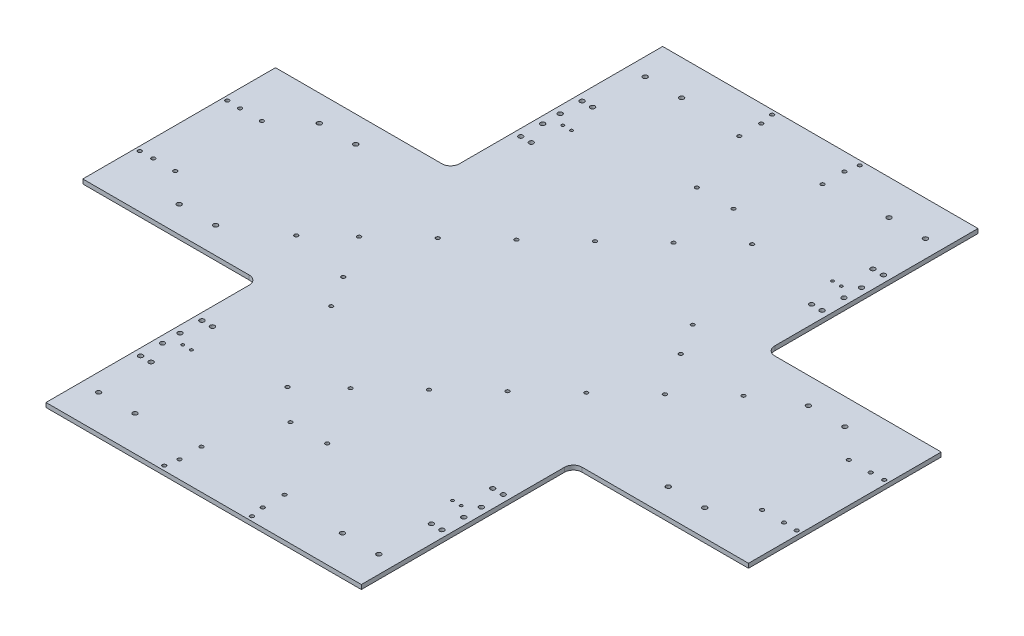
SolidWorks part; units mm, degrees
other "Markup1"
sketch "Sketch8"
material "3.0205 (EN-AW 1200)"
ref_plane "前视基准面" through (0, 0, 0) normal (0, 0, 1) x (1, 0, 0)
ref_plane "上视基准面" through (0, 0, 0) normal (0, 1, 0) x (1, 0, 0)
ref_plane "右视基准面" through (0, 0, 0) normal (1, 0, 0) x (0, 0, -1)
other "Configuration Table"
sketch "Sketch1" plane through (0, 0, 0) normal (0, 1, 0) x (1, 0, 0)
  line L0 (180, 352) -> (-180, 352)
  line L1 (-180, 352) -> (-180, 110)
  line L2 (-180, 110) -> (-380, 110)
  line L5 (-380, 110) -> (-380, -110)
  line L6 (0, 352) -> (0, -66.8675) construction
  line L7 (-380, 0) -> (131.0517, 0) construction
  line L8 (380, 110) -> (380, -110)
  line L11 (180, 110) -> (380, 110)
  line L12 (180, 352) -> (180, 110)
  line L13 (180, -352) -> (180, -110)
  line L14 (180, -110) -> (380, -110)
  line L19 (-180, -110) -> (-380, -110)
  line L20 (-180, -352) -> (-180, -110)
  line L21 (180, -352) -> (-180, -352)
  point P21 (380, 0)
  dimension "D1" = 180
  dimension "D2" = 200
  dimension "D3" = 110
  dimension "D4" = 242
extrude "Boss-Extrude1" add sketch "Sketch1" along normal blind 5
sketch "Sketch2" plane through (0, 5, 0) normal (0, 1, 0) x (1, 0, 0)
  line L3 (380, -110) -> (380, 110) construction
  line L4 (-56.7455, 0) -> (47.5165, 0) construction
  line L5 (0, 54.7142) -> (0, -64.2255) construction
  line L7 (180, 352) -> (-180, 352) construction
  circle A0 centre (360, 49.5) radius 2.125
  circle A1 centre (335, 49.5) radius 2.125
  circle A7 centre (335, -49.5) radius 2.125
  circle A8 centre (360, -49.5) radius 2.125
  circle A9 centre (-360, -49.5) radius 2.125
  circle A10 centre (-335, -49.5) radius 2.125
  circle A13 centre (-335, 49.5) radius 2.125
  circle A14 centre (-360, 49.5) radius 2.125
  circle A15 centre (47.5, 332) radius 2.125
  circle A16 centre (47.5, 307) radius 2.125
  circle A17 centre (-47.5, 307) radius 2.125
  circle A18 centre (-47.5, 332) radius 2.125
  circle A19 centre (-47.5, -332) radius 2.125
  circle A20 centre (-47.5, -307) radius 2.125
  circle A21 centre (47.5, -307) radius 2.125
  circle A22 centre (47.5, -332) radius 2.125
  dimension "D3" = 49.5
  dimension "D5" = 4.25
  dimension "D7" = 4.25
  dimension "D9" = 4.25
  dimension "D10" = 4.25
  dimension "D2" = 47.5
  dimension "D4" = 25
  dimension "D6" = 20
  dimension "20" = 20
  dimension "D13" = 25
extrude "Cut-Extrude1" cut sketch "Sketch2" against normal blind 3
sketch "Sketch4" plane through (0, 5, 0) normal (0, 1, 0) x (1, 0, 0)
  line L0 (-180, 352) -> (-180, 110) construction
  line L1 (180, 352) -> (-180, 352) construction
  line L2 (0, 46.9886) -> (0, -40.2904) construction
  line L3 (-35.103, 0) -> (92.4951, 0) construction
  line L5 (180, -352) -> (180, -110) construction
  circle A0 centre (-172, 182) radius 2.6
  circle A1 centre (-160, 182) radius 2.6
  circle A2 centre (-172, 207) radius 2.6
  circle A3 centre (-172, 227) radius 2.6
  circle A4 centre (-172, 252) radius 2.6
  circle A5 centre (-160, 252) radius 2.6
  circle A6 centre (160, 252) radius 2.6
  circle A7 centre (172, 252) radius 2.6
  circle A8 centre (172, 227) radius 2.6
  circle A9 centre (172, 207) radius 2.6
  circle A10 centre (160, 182) radius 2.6
  circle A11 centre (172, 182) radius 2.6
  circle A12 centre (172, -182) radius 2.6
  circle A13 centre (160, -182) radius 2.6
  circle A14 centre (172, -207) radius 2.6
  circle A15 centre (172, -227) radius 2.6
  circle A16 centre (172, -252) radius 2.6
  circle A17 centre (160, -252) radius 2.6
  circle A18 centre (-160, -252) radius 2.6
  circle A19 centre (-172, -252) radius 2.6
  circle A20 centre (-172, -227) radius 2.6
  circle A21 centre (-172, -207) radius 2.6
  circle A22 centre (-160, -182) radius 2.6
  circle A23 centre (-172, -182) radius 2.6
  circle A24 centre (159, -217) radius 1.6
  circle A25 centre (-159, -217) radius 1.6
  circle A26 centre (159, 217) radius 1.6
  circle A27 centre (-159, 217) radius 1.6
  circle A28 centre (149, -217) radius 1.6
  circle A29 centre (-149, -217) radius 1.6
  circle A30 centre (149, 217) radius 1.6
  circle A31 centre (-149, 217) radius 1.6
  dimension "D3" = 5.2
  dimension "D4" = 5.2
  dimension "D5" = 8
  dimension "D6" = 8
  dimension "D9" = 5.2
  dimension "D10" = 5.2
  dimension "D11" = 5.2
  dimension "D12" = 5.2
  dimension "D19" = 3.2
  dimension "D20" = 21
  dimension "D21" = 10
  dimension "D22" = 3.2
  dimension "D23" = 10
  dimension "D1" = 8
  dimension "D2" = 20
  dimension "D7" = 8
  dimension "D8" = 20
  dimension "D13" = 25
  dimension "D14" = 20
  dimension "D15" = 25
  dimension "D16" = 25
  dimension "D17" = 100
  dimension "D18" = 0
extrude "Cut-Extrude3" cut sketch "Sketch4" against normal blind 10
sketch "Sketch5" plane through (0, 5, 0) normal (0, 1, 0) x (1, 0, 0)
  line L0 (180, 352) -> (-180, 352) construction
  line L5 (-46.9195, 0) -> (66.6223, 0) construction
  line L6 (0, 59.0569) -> (0, -54.4849) construction
  line L10 (-380, 110) -> (-380, -110) construction
  circle A0 centre (-50, 347) radius 2.125
  circle A1 centre (50, 347) radius 2.125
  circle A2 centre (50, -347) radius 2.125
  circle A3 centre (-50, -347) radius 2.125
  circle A4 centre (-375, 50) radius 2.125
  circle A5 centre (-375, -50) radius 2.125
  circle A6 centre (375, -50) radius 2.125
  circle A7 centre (375, 50) radius 2.125
  dimension "D1" = 4.25
  dimension "D2" = 4.25
  dimension "D3" = 50
  dimension "D6" = 4.25
  dimension "D7" = 4.25
  dimension "5" = 5
  dimension "D4" = 50
  dimension "D5" = 50
  dimension "D8" = 50
  dimension "D9" = 5
  dimension "D10" = 5
extrude "Cut-Extrude4" cut sketch "Sketch5" against normal blind 10
fillet "Fillet1" radius 10 4 edges at (-180, 2.5, -110) (-180, 2.5, 110) (180, 2.5, 110) (180, 2.5, -110)
sketch "Sketch6" plane through (0, 5, 0) normal (0, 1, 0) x (1, 0, 0)
  line L0 (180, 352) -> (-180, 352) construction
  line L1 (-180, 352) -> (-180, 120) construction
  line L3 (0, 50.3702) -> (0, -42.7646) construction
  line L4 (-54.8568, 0) -> (91.2004, 0) construction
  line L5 (380, 110) -> (190, 110) construction
  line L6 (380, -110) -> (380, 110) construction
  circle A0 centre (-160, 312) radius 2.6
  circle A1 centre (-118.4, 312) radius 2.6
  circle A4 centre (118.4, 312) radius 2.6
  circle A5 centre (160, 312) radius 2.6
  circle A6 centre (160, -312) radius 2.6
  circle A7 centre (118.4, -312) radius 2.6
  circle A8 centre (-118.4, -312) radius 2.6
  circle A9 centre (-160, -312) radius 2.6
  circle A10 centre (258.4, 80) radius 2.6
  circle A11 centre (300, 80) radius 2.6
  circle A12 centre (300, -80) radius 2.6
  circle A13 centre (258.4, -80) radius 2.6
  circle A14 centre (-258.4, -80) radius 2.6
  circle A15 centre (-300, -80) radius 2.6
  circle A16 centre (-300, 80) radius 2.6
  circle A17 centre (-258.4, 80) radius 2.6
  dimension "D1" = 5.2
  dimension "D2" = 5.2
  dimension "D3" = 5.2
  dimension "D4" = 5.2
  dimension "D5" = 40
  dimension "D8" = 30
  dimension "D6" = 20
  dimension "D7" = 41.6
  dimension "D9" = 80
  dimension "D10" = 41.6
extrude "Cut-Extrude5" cut sketch "Sketch6" against normal blind 10
sketch "Sketch7" plane through (0, 5, 0) normal (0, 1, 0) x (1, 0, 0)
  line L0 (164.5832, 153.9982) -> (-155.4181, -145.4226) construction
  line L1 (180, 313.5897) -> (-272.7048, -110) construction
  line L2 (180, 120) -> (180, 352) construction
  line L3 (-380, -110) -> (-190, -110) construction
  line L4 (272.7048, 110) -> (-180, -313.5897) construction
  line L5 (380, 110) -> (190, 110) construction
  line L6 (-180, -120) -> (-180, -352) construction
  line L7 (-268.9942, -53.3124) -> (-51.1439, -286.1364) construction
  line L8 (84.7791, 253.9237) -> (328.5288, -6.5799) construction
  line L9 (-72.423, 77.401) -> (72.423, -77.401) construction
  line L11 (-380.0049, -355.5654) -> (380.0049, -355.5654) construction
  line L12 (-380.0049, -355.5654) -> (-380.0049, 355.5654) construction
  line L13 (-380.0049, 355.5654) -> (380.0049, 355.5654) construction
  line L14 (380.0049, -355.5654) -> (380.0049, 355.5654) construction
  line L15 (-380.0049, -355.5654) -> (380.0049, 355.5654) construction
  line L16 (-380.0049, 355.5654) -> (380.0049, -355.5654) construction
  circle A4 centre (-72.423, 77.401) radius 2.125
  circle A5 centre (-26.0555, 120.7864) radius 2.125
  circle A6 centre (20.3121, 164.1719) radius 2.125
  circle A7 centre (66.6796, 207.5574) radius 2.125
  circle A8 centre (-118.7906, 34.0155) radius 2.125
  circle A9 centre (-165.1581, -9.37) radius 2.125
  circle A10 centre (-202.2522, -44.0784) radius 2.125
  circle A11 centre (-57.4061, -198.8803) radius 2.125
  circle A12 centre (-20.3121, -164.1719) radius 2.125
  circle A13 centre (26.0555, -120.7864) radius 2.125
  circle A14 centre (211.5257, 52.7555) radius 2.125
  circle A15 centre (165.1581, 9.37) radius 2.125
  circle A16 centre (118.7906, -34.0155) radius 2.125
  circle A17 centre (72.423, -77.401) radius 2.125
  point P2 (164.8804, 152.7421)
  point P3 (0, 0)
  point P4 (-156.6685, -145.1348)
  point P53 (0, 0)
  point P58 (180, 110)
  dimension "D6" = 4.25
  dimension "D7" = 4.25
  dimension "D8" = 4.25
  dimension "D9" = 4.25
  dimension "D10" = 4.25
  dimension "D11" = 4.25
  dimension "D12" = 4.25
  dimension "D1" = 106
  dimension "D3" = 20
  dimension "D4" = 20
  dimension "D5" = 0
  dimension "D13" = 63.5
  dimension "D14" = 63.5
  dimension "D15" = 50.8
  dimension "D16" = 63.5
  dimension "D17" = 63.5
  dimension "D18" = 63.5
extrude "Cut-Extrude6" cut sketch "Sketch7" against normal blind 10
sketch "Sketch9" plane through (0, 5, 0) normal (0, 1, 0) x (1, 0, 0)
  line L0 (182.9289, 112.9289) -> (-182.9289, -112.9289) construction
  line L1 (92.6836, 125.8571) -> (158.1979, 19.7331) construction
  line L2 (-151.014, -31.37) -> (-99.0832, -115.4905) construction
  line L3 (0, 45.0584) -> (0, -52.9183) construction
  line L4 (-44.6513, 0) -> (48.0404, 0) construction
  line L5 (180, 352) -> (-180, 352) construction
  arc A0 (180, 120) -> (190, 110) centre (190, 120) ccw construction
  arc A1 (-180, -120) -> (-190, -110) centre (-190, -120) ccw construction
  circle A2 centre (-134.3962, -58.2885) radius 2.1
  circle A3 centre (-112.3335, -94.027) radius 2.1
  circle A4 centre (112.3335, 94.027) radius 2.1
  circle A5 centre (134.3962, 58.2885) radius 2.1
  circle A7 centre (21, 232) radius 2.1
  circle A8 centre (-21, 232) radius 2.1
  circle A9 centre (-21, -232) radius 2.1
  circle A10 centre (21, -232) radius 2.1
  dimension "D3" = 4.2
  dimension "D4" = 4.2
  dimension "D5" = 4.2
  dimension "D6" = 4.2
  dimension "D11" = 120
  dimension "D12" = 4.2
  dimension "D1" = 70
  dimension "D2" = 70
  dimension "D7" = 21
  dimension "D8" = 21
  dimension "D9" = 21
  dimension "D10" = 21
  dimension "D13" = 21
extrude "Cut-Extrude7" cut sketch "Sketch9" against normal blind 10
